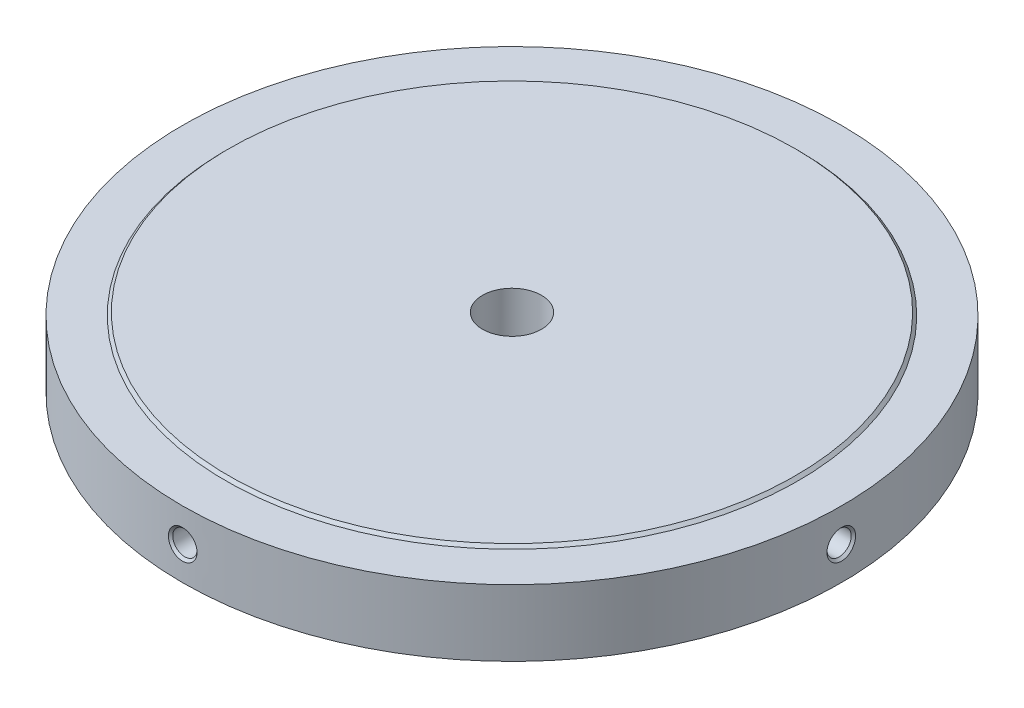
SolidWorks part; units mm, degrees
material "Polyetheretherketone (PEEK)"
ref_plane "Front Plane" through (0, 0, 0) normal (0, 0, 1) x (1, 0, 0)
ref_plane "Top Plane" through (0, 0, 0) normal (0, 1, 0) x (1, 0, 0)
ref_plane "Right Plane" through (0, 0, 0) normal (1, 0, 0) x (0, 0, -1)
sketch "Sketch1" plane through (0, 0, 0) normal (0, 0, 1) x (1, 0, 0)
  line L0 (0, 0) -> (0, 50000) construction
  line L1 (0, 6.25) -> (49, 6.25)
  line L3 (0, 6.25) -> (0, -5.75)
  line L4 (0, -5.75) -> (57, -5.75)
  line L5 (57, 5.75) -> (57, -5.75)
  line L7 (57, 5.75) -> (49.5, 5.75)
  line L10 (49, 6.25) -> (49.5, 5.75)
  point P7 (57, 0)
  dimension "D1" = 11.5
  dimension "D2" = 114
  dimension "D3" = 98
  dimension "D4" = 0.5
  dimension "D5" = 0.5
revolve "Revolve1" add sketch "Sketch1" angle 360 about L0
hole_wizard "M5 Tapped Hole1" positions "3DSketch1" profile "Sketch2" tap size "M5" standard "ISO"
sketch3d "3DSketch1"
  circle A0 centre (0, 0, 0) radius 57 construction
  point P0 (57, 0, 0)
  point P2 (0, 0, 57)
  point P4 (-57, 0, 0)
  point P6 (0, 0, -57)
  point P11 (0, 57, 0)
sketch "Sketch2" plane through (57, 0, 0) normal (0, 1, 0) x (0, 0, -1)
  line L0 (0, 0) -> (0, 15.2618)
  line L1 (0, 15.2618) -> (2.1, 14)
  line L2 (2.1, 14) -> (2.1, 0.425)
  line L3 (2.1, 0.425) -> (2.525, 0)
  line L5 (2.525, 0) -> (0, 0)
  line L6 (-2.1, 0.425) -> (-2.525, 0) construction
  line L10 (0, 15.2618) -> (-2.1, 14) construction
  line L11 (0, -6.35) -> (0, 107.95) construction
  dimension "Tap Drill Dia." = 4.2
  dimension "Tap Drill Depth" = 14
  dimension "Near C'Sink Dia." = 5.05
  dimension "Near C'Sink Angle" = 90
  dimension "Drill Angle" = 118
cosmetic thread "Hole Thread6"
cosmetic thread "Hole Thread7"
cosmetic thread "Hole Thread8"
cosmetic thread "Hole Thread9"
hole_wizard "M12 Tapped Hole1" positions "Sketch3" profile "Sketch4" tap size "M12" standard "ISO" end condition up to next
sketch "Sketch3" plane through (0, 6.25, 0) normal (0, 1, 0) x (1, 0, 0)
  point P2 (0, 0)
sketch "Sketch4" plane through (0, 6.25, 0) normal (1, 0, 0) x (0, 0, 1)
  line L0 (0, 0) -> (0, 12)
  line L1 (0, 12) -> (5.1, 12)
  line L2 (5.1, 12) -> (5.1, 0)
  line L5 (5.1, 0) -> (0, 0)
  line L11 (0, -6.35) -> (0, 107.95) construction
  dimension "Thru Tap Drill Dia." = 10.2
  dimension "Thru Tap Drill Depth" = 12
cosmetic thread "Hole Thread10" parameters "D2"=12
equation "\"CanSat_Len\"= 400mm"
equation "\"CanSat_Dia\"= 150mm"
equation "\"BodyTube_ID\"= 114mm"
equation "\"BodyTube_OD\"= 120mm"
equation "\"PayLoadBay_ID\"= 164mm"
equation "\"PayLoadBay_OD\"= 170mm"
equation "\"ParachuteBay_Pitch\"= 300mm"
equation "\"ElectronicsTray_PitchDist\"= 40mm"
equation "\"ElectronicsTray_Height\"= 120mm"
equation "\"D2@Sketch1\"=\"BodyTube_ID\""
